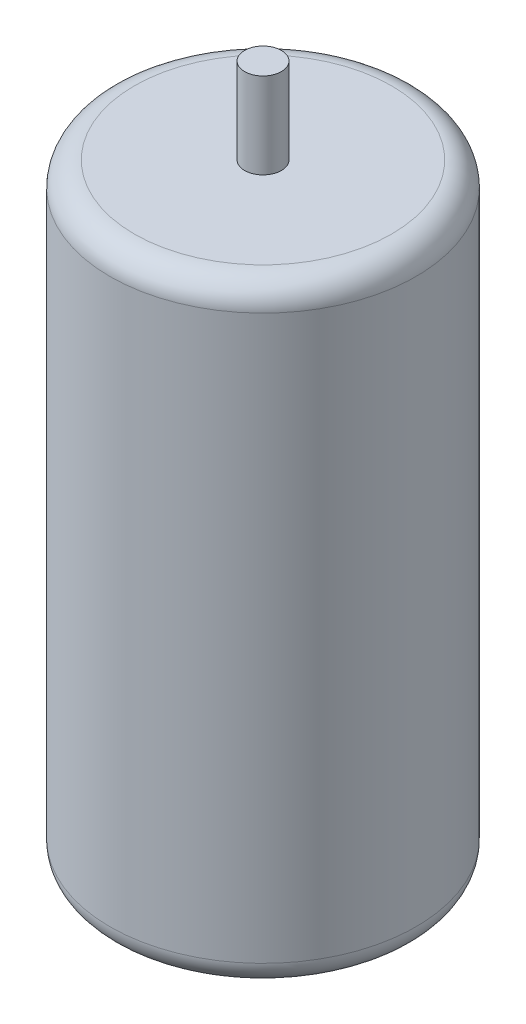
SolidWorks part; units mm, degrees
material "Alúmina"
ref_plane "Alzado" through (0, 0, 0) normal (0, 0, 1) x (1, 0, 0)
ref_plane "Planta" through (0, 0, 0) normal (0, 1, 0) x (1, 0, 0)
ref_plane "Vista lateral" through (0, 0, 0) normal (1, 0, 0) x (0, 0, -1)
sketch "Croquis2" plane through (0, 0, 0) normal (0, 1, 0) x (1, 0, 0)
  circle A0 centre (0, 0) radius 12.5
  dimension "D1" = 25
extrude "Saliente-Extruir1" add sketch "Croquis2" along normal blind 50
sketch "Croquis3" plane through (0, 0, 0) normal (0, -1, 0) x (1, 0, 0)
  circle A0 centre (0, 0) radius 12.5
fillet "Redondeo1" radius 2 2 edges at (0, 0, 12.5) (0, 50, 12.5)
sketch "Croquis4" plane through (0, 50, 0) normal (0, 1, 0) x (1, 0, 0)
  circle A0 centre (0, 0) radius 1.5
  dimension "D1" = 3
extrude "Saliente-Extruir2" add sketch "Croquis4" along normal blind 7
sketch "Croquis5" plane through (0, 0, 0) normal (0, -1, 0) x (-1, 0, 0)
  line L0 (0, 0) -> (-5.0025, 0)
  line L1 (-5.0025, 0) -> (4.9975, 0)
  line L2 (0, 0) -> (0, -8.869)
  line L3 (-4.5363, 1.4818) -> (-5.4686, 1.4818)
  line L4 (-4.5363, 1.4818) -> (-4.5363, -1.4818)
  line L5 (-4.5363, -1.4818) -> (-5.4686, -1.4818)
  line L6 (-5.4686, 1.4818) -> (-5.4686, -1.4818)
  line L7 (-4.5363, 1.4818) -> (-5.4686, -1.4818) construction
  line L8 (-4.5363, -1.4818) -> (-5.4686, 1.4818) construction
  line L9 (4.5363, 1.4818) -> (5.4686, 1.4818)
  line L10 (4.5363, -1.4818) -> (5.4686, -1.4818)
  line L11 (4.5363, 1.4818) -> (4.5363, -1.4818)
  line L12 (5.4686, 1.4818) -> (5.4686, -1.4818)
  dimension "D1" = 10
extrude "Saliente-Extruir3" add sketch "Croquis5" along normal blind 4 contours L12 L9 L11 L10 | L3 L6 L5 L4 region at (4.5673, 0, 0.7409) region at (-5.0025, 0, 0)
fillet "Redondeo2" radius 2 4 edges at (5.0025, -4, -1.4818) (5.0025, -4, 1.4818) (-5.0025, -4, 1.4818) (-5.0025, -4, -1.4818)
sketch "Croquis6" plane through (5.4686, 0, 0) normal (1, 0, 0) x (0, 0, -1)
  circle A0 centre (0, -2) radius 0.8144
extrude "Cortar-Extruir3" cut sketch "Croquis6" against normal blind 18
